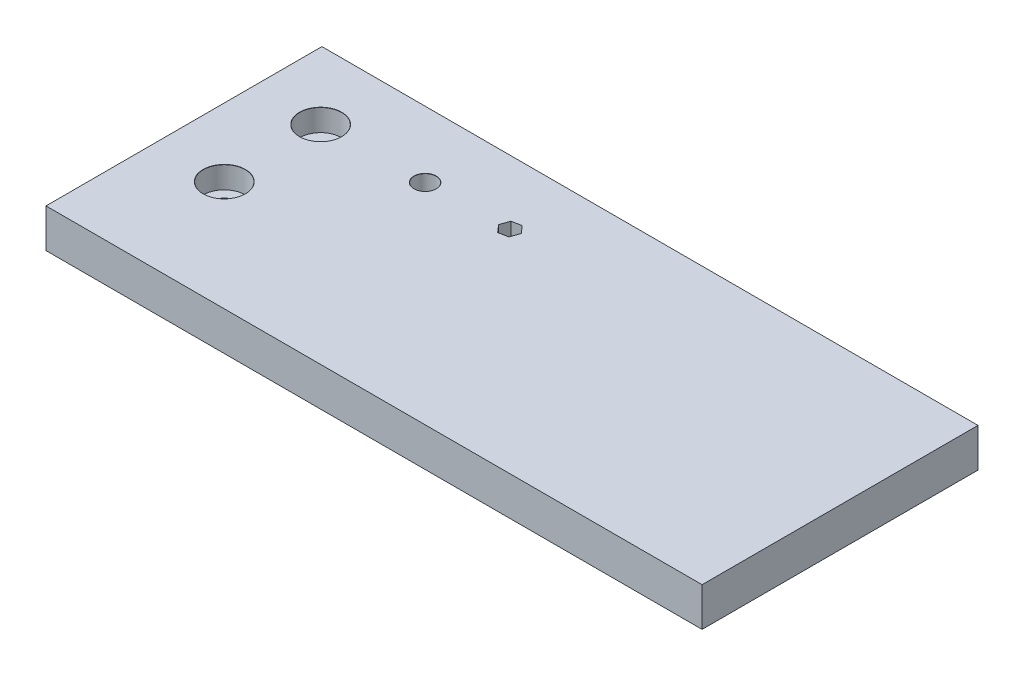
SolidWorks part; units mm, degrees
ref_plane "Front Plane" through (0, 0, 0) normal (0, 0, 1) x (1, 0, 0)
ref_plane "Top Plane" through (0, 0, 0) normal (0, 1, 0) x (1, 0, 0)
ref_plane "Right Plane" through (0, 0, 0) normal (1, 0, 0) x (0, 0, -1)
sketch "Sketch1" plane through (0, 0, 0) normal (0, 1, 0) x (1, 0, 0)
  line L0 (-38.6508, 19.3444) -> (-38.5038, 20.1069)
  line L5 (-38.5038, 20.1069) -> (-38.7577, 20.8406)
  line L6 (-38.7577, 20.8406) -> (-39.3444, 21.3492)
  line L7 (-38.6508, 39.3444) -> (-38.5038, 40.1069)
  line L8 (-38.5038, 40.1069) -> (-38.7577, 40.8406)
  line L9 (-38.7577, 40.8406) -> (-39.3444, 41.3492)
  line L10 (-39.3444, 41.3492) -> (-40.1069, 41.4962)
  line L11 (-40.1069, 41.4962) -> (-40.8406, 41.2423)
  line L12 (-40.8406, 41.2423) -> (-41.3492, 40.6556)
  line L13 (-41.3492, 40.6556) -> (-41.4962, 39.8931)
  line L14 (-41.4962, 39.8931) -> (-41.2423, 39.1594)
  line L15 (-41.2423, 39.1594) -> (-40.6556, 38.6508)
  line L16 (-40.6556, 38.6508) -> (-39.8931, 38.5038)
  line L17 (-39.8931, 38.5038) -> (-39.1594, 38.7577)
  line L18 (-39.1594, 38.7577) -> (-38.6508, 39.3444)
  line L19 (-18.6508, 39.3444) -> (-18.5232, 40.2627)
  line L20 (-18.5232, 40.2627) -> (-18.9596, 41.0806)
  line L21 (-18.9596, 41.0806) -> (-19.7934, 41.4857)
  line L22 (-19.7934, 41.4857) -> (-20.7062, 41.3234)
  line L23 (-20.7062, 41.3234) -> (-21.3492, 40.6556)
  line L24 (-21.3492, 40.6556) -> (-21.4768, 39.7373)
  line L25 (-21.4768, 39.7373) -> (-21.0404, 38.9194)
  line L26 (-21.0404, 38.9194) -> (-20.2066, 38.5143)
  line L27 (-20.2066, 38.5143) -> (-19.2938, 38.6766)
  line L28 (-19.2938, 38.6766) -> (-18.6508, 39.3444)
  line L29 (1.0404, 38.9194) -> (1.4997, 39.9716)
  line L30 (1.4997, 39.9716) -> (1.0806, 41.0404)
  line L31 (1.0806, 41.0404) -> (0.0284, 41.4997)
  line L32 (0.0284, 41.4997) -> (-1.0404, 41.0806)
  line L33 (-1.0404, 41.0806) -> (-1.4997, 40.0284)
  line L34 (-1.4997, 40.0284) -> (-1.0806, 38.9596)
  line L35 (-1.0806, 38.9596) -> (-0.0284, 38.5003)
  line L36 (-0.0284, 38.5003) -> (1.0404, 38.9194)
  line L37 (21.4768, 39.7373) -> (20.9659, 41.1476)
  line L38 (20.9659, 41.1476) -> (19.4891, 41.4103)
  line L39 (19.4891, 41.4103) -> (18.5232, 40.2627)
  line L40 (18.5232, 40.2627) -> (19.0341, 38.8524)
  line L41 (19.0341, 38.8524) -> (20.5109, 38.5897)
  line L42 (20.5109, 38.5897) -> (21.4768, 39.7373)
  line L43 (41.3914, 39.4395) -> (40.5605, 41.3914)
  line L44 (40.5605, 41.3914) -> (38.6086, 40.5605)
  line L45 (38.6086, 40.5605) -> (39.4395, 38.6086)
  line L46 (39.4395, 38.6086) -> (41.3914, 39.4395)
  line L47 (-39.3444, 21.3492) -> (-40.1069, 21.4962)
  line L48 (-40.1069, 21.4962) -> (-40.8406, 21.2423)
  line L49 (-40.8406, 21.2423) -> (-41.3492, 20.6556)
  line L50 (-41.3492, 20.6556) -> (-41.4962, 19.8931)
  line L51 (-41.4962, 19.8931) -> (-41.2423, 19.1594)
  line L52 (-41.2423, 19.1594) -> (-40.6556, 18.6508)
  line L53 (-40.6556, 18.6508) -> (-39.8931, 18.5038)
  line L54 (-39.8931, 18.5038) -> (-39.1594, 18.7577)
  line L55 (-39.1594, 18.7577) -> (-38.6508, 19.3444)
  line L56 (-18.6508, 19.3444) -> (-18.5232, 20.2627)
  line L57 (-18.5232, 20.2627) -> (-18.9596, 21.0806)
  line L58 (-18.9596, 21.0806) -> (-19.7934, 21.4857)
  line L59 (-19.7934, 21.4857) -> (-20.7062, 21.3234)
  line L60 (-20.7062, 21.3234) -> (-21.3492, 20.6556)
  line L61 (-21.3492, 20.6556) -> (-21.4768, 19.7373)
  line L62 (-21.4768, 19.7373) -> (-21.0404, 18.9194)
  line L63 (-21.0404, 18.9194) -> (-20.2066, 18.5143)
  line L64 (-20.2066, 18.5143) -> (-19.2938, 18.6766)
  line L65 (-19.2938, 18.6766) -> (-18.6508, 19.3444)
  line L66 (1.0404, 18.9194) -> (1.4997, 19.9716)
  line L67 (1.4997, 19.9716) -> (1.0806, 21.0404)
  line L68 (1.0806, 21.0404) -> (0.0284, 21.4997)
  line L69 (0.0284, 21.4997) -> (-1.0404, 21.0806)
  line L70 (-1.0404, 21.0806) -> (-1.4997, 20.0284)
  line L71 (-1.4997, 20.0284) -> (-1.0806, 18.9596)
  line L72 (-1.0806, 18.9596) -> (-0.0284, 18.5003)
  line L73 (-0.0284, 18.5003) -> (1.0404, 18.9194)
  line L74 (21.4768, 19.7373) -> (20.9659, 21.1476)
  line L75 (20.9659, 21.1476) -> (19.4891, 21.4103)
  line L76 (19.4891, 21.4103) -> (18.5232, 20.2627)
  line L77 (18.5232, 20.2627) -> (19.0341, 18.8524)
  line L78 (19.0341, 18.8524) -> (20.5109, 18.5897)
  line L79 (20.5109, 18.5897) -> (21.4768, 19.7373)
  line L80 (41.3914, 19.4395) -> (40.5605, 21.3914)
  line L81 (40.5605, 21.3914) -> (38.6086, 20.5605)
  line L82 (38.6086, 20.5605) -> (39.4395, 18.6086)
  line L83 (39.4395, 18.6086) -> (41.3914, 19.4395)
  line L85 (41.2145, -3.2425) -> (-60.3855, -3.2425)
  line L86 (41.2145, -3.2425) -> (41.2145, -45.9701)
  line L87 (41.2145, -45.9701) -> (-60.3855, -45.9701)
  line L88 (-60.3855, -3.2425) -> (-60.3855, -45.9701)
  circle A41 centre (-40, 40) radius 1.4489 construction
  circle A43 centre (-20, 40) radius 1.4266 construction
  circle A45 centre (0, 40) radius 1.3858 construction
  circle A47 centre (20, 40) radius 1.299 construction
  circle A49 centre (40, 40) radius 1.0607 construction
  circle A50 centre (-40, 20) radius 1.4489 construction
  circle A51 centre (-20, 20) radius 1.4266 construction
  circle A52 centre (0, 20) radius 1.3858 construction
  circle A53 centre (20, 20) radius 1.299 construction
  circle A54 centre (40, 20) radius 1.0607 construction
  point P2 (0, 0)
extrude "Boss-Extrude2" add sketch "Sketch1" along normal blind 6 contours L86 L85 L88 L87
sketch "Sketch3" plane through (0, 6, 0) normal (0, 1, 0) x (1, 0, 0)
sketch "Sketch6" plane through (0, 6, 0) normal (0, 1, 0) x (1, 0, 0)
  point P0 (-50.0443, -13.7823)
  point P2 (-50.0443, -13.7823)
hole_wizard "CBORE for M3 Hex Socket Head Cap Screw1" positions "Sketch6" profile "Sketch5" counterbore size "M3" standard "ISO" end condition through all
sketch "Sketch5" plane through (-50.0443, 6, 13.7823) normal (1, 0, 0) x (0, 0, 1)
  line L0 (0, 0) -> (0, 6)
  line L1 (0, 6) -> (1.6, 6)
  line L3 (1.6, 6) -> (1.6, 3.4)
  line L4 (3.25, 3.4) -> (1.6, 3.4)
  line L5 (3.25, 3.4) -> (3.25, 0.025)
  line L6 (3.25, 0.025) -> (3.275, 0)
  line L7 (3.275, 0) -> (0, 0)
  line L8 (-3.25, 0.025) -> (-3.275, 0) construction
  line L11 (0, -6.35) -> (0, 107.95) construction
  dimension "Thru Hole Dia." = 3.2
  dimension "Thru Hole Depth" = 6
  dimension "C'Bore Dia." = 6.5
  dimension "C'Bore Depth" = 3.4
  dimension "Near C'Sink Dia." = 6.55
  dimension "Near C'Sink Angle" = 90
sketch "Sketch9" plane through (0, 6, 0) normal (0, 1, 0) x (1, 0, 0)
  point P0 (-49.8341, -28.9149)
hole_wizard "CBORE for M3 Hex Socket Head Cap Screw2" positions "Sketch9" profile "Sketch8" counterbore size "M3" standard "ISO" end condition through all
sketch "Sketch8" plane through (-49.8341, 6, 28.9149) normal (1, 0, 0) x (0, 0, 1)
  line L0 (0, 0) -> (0, 6)
  line L1 (0, 6) -> (1.7, 6)
  line L3 (1.7, 6) -> (1.7, 3.4)
  line L4 (3.25, 3.4) -> (1.7, 3.4)
  line L5 (3.25, 3.4) -> (3.25, 0.025)
  line L6 (3.25, 0.025) -> (3.275, 0)
  line L7 (3.275, 0) -> (0, 0)
  line L8 (-3.25, 0.025) -> (-3.275, 0) construction
  line L11 (0, -6.35) -> (0, 107.95) construction
  dimension "Thru Hole Dia." = 3.4
  dimension "Thru Hole Depth" = 6
  dimension "C'Bore Dia." = 6.5
  dimension "C'Bore Depth" = 3.4
  dimension "Near C'Sink Dia." = 6.55
  dimension "Near C'Sink Angle" = 90
sketch "Sketch12" plane through (0, 6, 0) normal (0, 1, 0) x (1, 0, 0)
  point P0 (-32.2845, -13.3619)
sketch "Sketch16" plane through (0, 6, 0) normal (0, 1, 0) x (1, 0, 0)
  point P0 (-34.176, -13.467)
hole_wizard "M3 Clearance Hole1" positions "Sketch16" profile "Sketch15" hole size "M3" standard "ISO" end condition through all
sketch "Sketch15" plane through (-34.176, 6, 13.467) normal (1, 0, 0) x (0, 0, 1)
  line L0 (0, 0) -> (0, 6)
  line L1 (0, 6) -> (1.7, 6)
  line L2 (1.7, 6) -> (1.7, 0.025)
  line L3 (1.7, 0.025) -> (1.725, 0)
  line L5 (1.725, 0) -> (0, 0)
  line L6 (-1.7, 0.025) -> (-1.725, 0) construction
  line L11 (0, -6.35) -> (0, 107.95) construction
  dimension "Thru Hole Dia." = 3.4
  dimension "Thru Hole Depth" = 6
  dimension "Near C'Sink Dia." = 3.45
  dimension "Near C'Sink Angle" = 90
sketch "Sketch17" plane through (0, 6, 0) normal (0, 1, 0) x (1, 0, 0)
  line L1 (-20.3742, -14.2913) -> (-19.8822, -12.8743)
  line L2 (-19.8822, -12.8743) -> (-20.8633, -11.7397)
  line L3 (-20.8633, -11.7397) -> (-22.3365, -12.0221)
  line L4 (-22.3365, -12.0221) -> (-22.8285, -13.4391)
  line L5 (-22.8285, -13.4391) -> (-21.8473, -14.5737)
  line L6 (-21.8473, -14.5737) -> (-20.3742, -14.2913)
  circle A1 centre (-21.3553, -13.1567) radius 1.299 construction
extrude "Cut-Extrude1" cut sketch "Sketch17" against normal through all contours L5 L6 L1 L2 L3 L4 | L1 L2 L3 L4 L5 L6 region at (-21.3553, 6, 13.1567)
sketch "Sketch18" plane through (0, 6, 0) normal (0, 1, 0) x (1, 0, 0)
  line L1 (-6.4268, -13.5352) -> (-5.7993, -12.5738)
  line L2 (-5.7993, -12.5738) -> (-6.0355, -11.4503)
  line L3 (-6.0355, -11.4503) -> (-6.9969, -10.8228)
  line L4 (-6.9969, -10.8228) -> (-8.1204, -11.059)
  line L5 (-8.1204, -11.059) -> (-8.7478, -12.0204)
  line L6 (-8.7478, -12.0204) -> (-8.5117, -13.1439)
  line L7 (-8.5117, -13.1439) -> (-7.5503, -13.7714)
  line L8 (-7.5503, -13.7714) -> (-6.4268, -13.5352)
  line L9 (8.7046, -13.5352) -> (8.9557, -12.6428)
  line L10 (8.9557, -12.6428) -> (8.6343, -11.7733)
  line L11 (8.6343, -11.7733) -> (7.8632, -11.2587)
  line L12 (7.8632, -11.2587) -> (6.9369, -11.2956)
  line L13 (6.9369, -11.2956) -> (6.2092, -11.8699)
  line L14 (6.2092, -11.8699) -> (5.9581, -12.7623)
  line L15 (5.9581, -12.7623) -> (6.2795, -13.6319)
  line L16 (6.2795, -13.6319) -> (7.0506, -14.1465)
  line L17 (7.0506, -14.1465) -> (7.9769, -14.1096)
  line L18 (7.9769, -14.1096) -> (8.7046, -13.5352)
  line L19 (22.4019, -13.7714) -> (22.7953, -13.1019)
  line L20 (22.7953, -13.1019) -> (22.8012, -12.3255)
  line L21 (22.8012, -12.3255) -> (22.4182, -11.6501)
  line L22 (22.4182, -11.6501) -> (21.7488, -11.2567)
  line L23 (21.7488, -11.2567) -> (20.9723, -11.2507)
  line L24 (20.9723, -11.2507) -> (20.2969, -11.6338)
  line L25 (20.2969, -11.6338) -> (19.9035, -12.3032)
  line L26 (19.9035, -12.3032) -> (19.8976, -13.0796)
  line L27 (19.8976, -13.0796) -> (20.2806, -13.755)
  line L28 (20.2806, -13.755) -> (20.95, -14.1484)
  line L29 (20.95, -14.1484) -> (21.7265, -14.1544)
  line L30 (21.7265, -14.1544) -> (22.4019, -13.7714)
  line L31 (34.169, -13.9771) -> (34.6436, -13.5077)
  line L32 (34.6436, -13.5077) -> (34.8676, -12.8788)
  line L33 (34.8676, -12.8788) -> (34.7965, -12.215)
  line L34 (34.7965, -12.215) -> (34.4445, -11.6478)
  line L35 (34.4445, -11.6478) -> (33.8812, -11.2895)
  line L36 (33.8812, -11.2895) -> (33.2183, -11.2111)
  line L37 (33.2183, -11.2111) -> (32.587, -11.4281)
  line L38 (32.587, -11.4281) -> (32.1123, -11.8975)
  line L39 (32.1123, -11.8975) -> (31.8884, -12.5264)
  line L40 (31.8884, -12.5264) -> (31.9594, -13.1901)
  line L41 (31.9594, -13.1901) -> (32.3115, -13.7573)
  line L42 (32.3115, -13.7573) -> (32.8747, -14.1156)
  line L43 (32.8747, -14.1156) -> (33.5377, -14.1941)
  line L44 (33.5377, -14.1941) -> (34.169, -13.9771)
  circle A4 centre (-7.2736, -12.2971) radius 1.3858 construction
  circle A5 centre (7.4569, -12.7026) radius 1.4266 construction
  circle A6 centre (21.3494, -12.7026) radius 1.4489 construction
  circle A7 centre (33.378, -12.7026) radius 1.4624 construction
